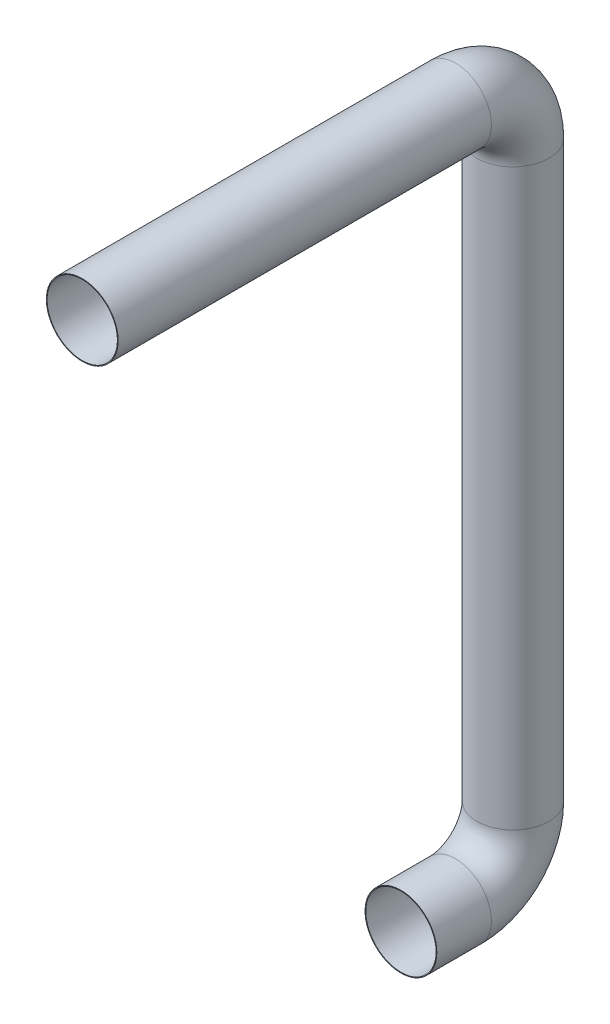
SolidWorks part; units mm, degrees
material "AISI 316 Stainless Steel Sheet (SS)"
ref_plane "Front Plane" through (0, 0, 0) normal (0, 0, 1) x (1, 0, 0)
ref_plane "Top Plane" through (0, 0, 0) normal (0, 1, 0) x (1, 0, 0)
ref_plane "Right Plane" through (0, 0, 0) normal (1, 0, 0) x (0, 0, -1)
sketch "Sketch31" plane through (0, 0, 0) normal (0, 0, 1) x (1, 0, 0)
  circle A0 centre (0, 0) radius 24.5
  circle A1 centre (0, 0) radius 25
  dimension "D1" = 50
  dimension "D2" = 0.5
sketch "Sketch3" plane through (0, 0, 0) normal (1, 0, 0) x (0, 0, -1)
  line L0 (0, 0) -> (260, 0)
  line L1 (300, -40) -> (300, -440)
  line L2 (260, -480) -> (222, -480)
  arc A0 (260, 0) -> (300, -40) centre (260, -40) cw
  arc A1 (300, -440) -> (260, -480) centre (260, -440) cw
  dimension "D1" = 300
  dimension "D3" = 40
  dimension "D2" = 400
  dimension "D4" = 38
sweep "Sweep1" add profiles "Sketch31" path "Sketch3"
